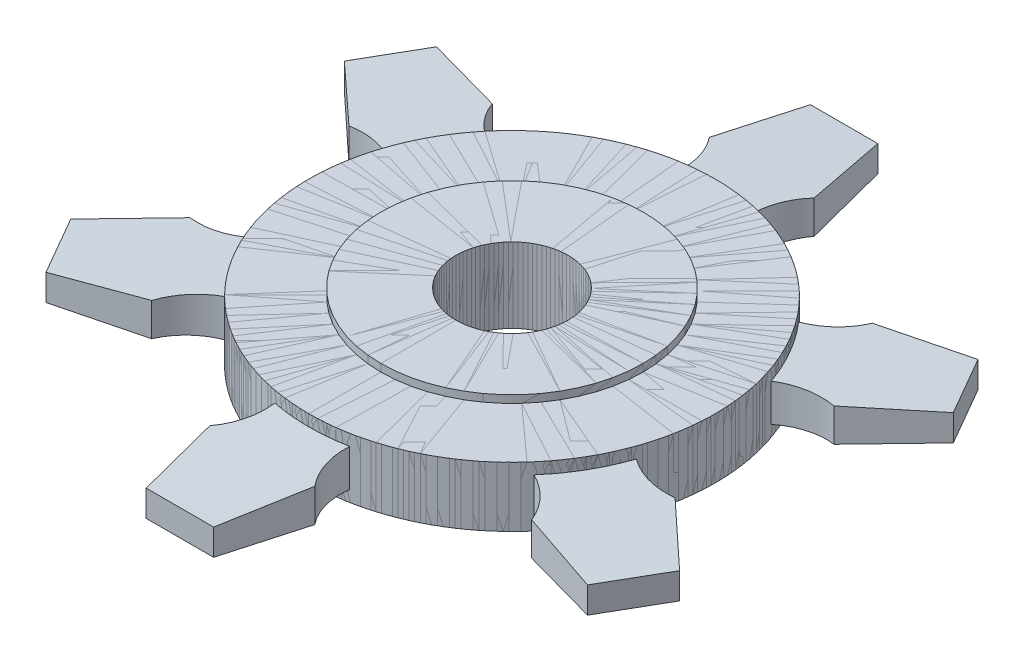
SolidWorks part; units mm, degrees
ref_plane "前视基准面" through (0, 0, 0) normal (0, 0, 1) x (1, 0, 0)
ref_plane "上视基准面" through (0, 0, 0) normal (0, 1, 0) x (1, 0, 0)
ref_plane "右视基准面" through (0, 0, 0) normal (1, 0, 0) x (0, 0, -1)
other "Configuration Table"
sketch "草图1" plane through (0, 0, 0) normal (0, 1, 0) x (1, 0, 0)
  line L0 (-22.9143, 0) -> (22.9207, 0) construction
  line L1 (0, 75.1047) -> (0, -18.5417) construction
  line L2 (-4.5, 44.3205) -> (4.5, 44.3205)
  line L11 (-10, 37.3205) -> (-27.3205, 27.3205)
  line L12 (-27.3205, 27.3205) -> (-37.3205, 10)
  line L13 (-37.3205, 10) -> (-37.3205, -10)
  line L14 (-37.3205, -10) -> (-27.3205, -27.3205)
  line L15 (-27.3205, -27.3205) -> (-10, -37.3205)
  line L16 (-10, -37.3205) -> (10, -37.3205)
  line L17 (10, -37.3205) -> (27.3205, -27.3205)
  line L18 (27.3205, -27.3205) -> (37.3205, -10)
  line L19 (37.3205, -10) -> (37.3205, 10)
  line L20 (37.3205, 10) -> (27.3205, 27.3205)
  line L21 (27.3205, 27.3205) -> (10, 37.3205)
  line L22 (10, 37.3205) -> (-10, 37.3205)
  line L23 (-7, 33.3205) -> (7, 33.3205) construction
  line L24 (-4.5, 44.3205) -> (-7, 33.3205)
  line L25 (4.5, 44.3205) -> (7, 33.3205)
  circle A0 centre (0, 0) radius 7.5
  circle A1 centre (0, 0) radius 17.5
  circle A2 centre (0, 0) radius 37.3205 construction
  circle A3 centre (0, 0) radius 27.125
  arc A4 (-7, 33.3205) -> (-5, 26.6602) centre (-14.0668, 27.568) cw
  arc A5 (7, 33.3205) -> (5, 26.6602) centre (14.0668, 27.568) ccw
  point P24 (0, 33.3205)
  point P25 (0, 44.3205)
  dimension "D1" = 15
  dimension "D2" = 35
  dimension "D4" = 11
  dimension "D7" = 54.25
  dimension "D8" = 9
  dimension "D9" = 5
  dimension "D3" = 20
  dimension "D5" = 7
  dimension "D6" = 14
ref_axis "基准轴1" through (0, 5.5, 0) along (0, -1, 0)
extrude "凸台-拉伸2" add sketch "草图1" along normal mid plane 5 contours L25 L2 L24 L22 | A5 L25 L22 L24 A4 A3 region at (0, 0, -40.6453) region at (0, 0, -32.4404)
sketch "草图4" plane through (0, 0, 0) normal (1, 0, 0) x (0, 0, -1)
  line L0 (26.6602, 2.5) -> (44.3205, 1.75)
  line L1 (44.3205, 2.5) -> (44.3205, -2.5) construction
  line L2 (44.3205, 1.75) -> (44.3205, -1.75)
  line L3 (44.3205, -1.75) -> (26.6602, -2.5)
  line L4 (26.6602, 2.5) -> (26.6602, -2.5)
  dimension "D1" = 3.5
  dimension "D2" = 0.75
extrude "切除-拉伸1" cut sketch "草图4" against normal mid plane 20 flip side to cut
extrude "凸台-拉伸3" add sketch "草图1<7>" along normal mid plane 8 contours A3 A1 region at (0, 0, -26.3578)
sketch "草图1<7>" plane through (0, 0, 0) normal (0, 1, 0) x (1, 0, 0) same geometry as "草图1"
extrude "凸台-拉伸4" add sketch "草图1<8>" along normal mid plane 10 contours A1 A0 region at (-17.005, 0, 0)
sketch "草图1<8>" plane through (0, 0, 0) normal (0, 1, 0) x (1, 0, 0) same geometry as "草图1"
pattern_circular "阵列(圆周)3" count 6 over 360 about axis through (0, 5.5, 0) along (0, -1, 0) of bodies 119
